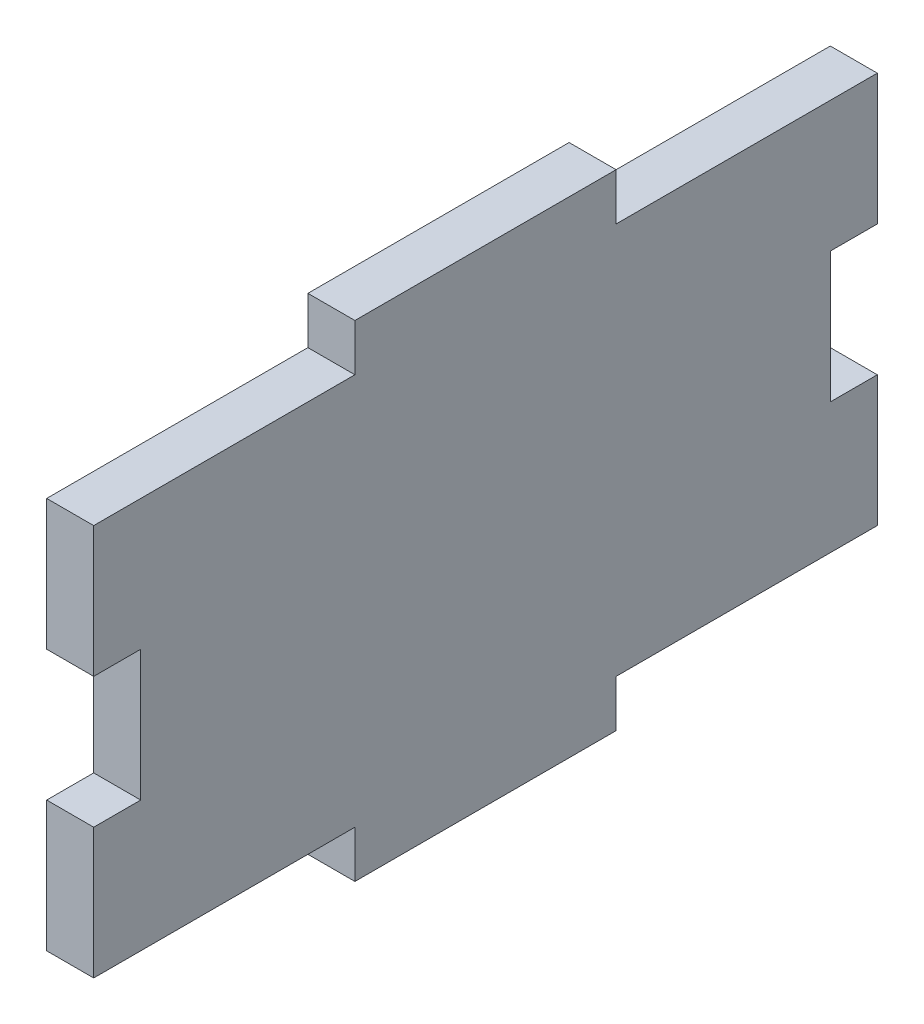
SolidWorks part; units mm, degrees
ref_plane "Front Plane" through (0, 0, 0) normal (0, 0, 1) x (1, 0, 0)
ref_plane "Top Plane" through (0, 0, 0) normal (0, 1, 0) x (1, 0, 0)
ref_plane "Right Plane" through (0, 0, 0) normal (1, 0, 0) x (0, 0, -1)
sketch "Sides" plane through (0, 0, 0) normal (1, 0, 0) x (0, 0, -1)
  line L0 (0, 16.6667) -> (0, 25)
  line L1 (0, 0) -> (16.6667, 0)
  line L2 (0, 0) -> (0, 8.3333)
  line L3 (0, 25) -> (16.6667, 25)
  line L4 (50, 0) -> (50, 8.3333)
  line L5 (0, 16.6667) -> (3, 16.6667)
  line L6 (33.3333, 25) -> (50, 25)
  line L7 (0, 8.3333) -> (3, 8.3333)
  line L8 (3, 16.6667) -> (3, 8.3333)
  line L9 (33.3333, 0) -> (50, 0)
  line L10 (16.6667, 25) -> (16.6667, 28)
  line L11 (16.6667, 28) -> (33.3333, 28)
  line L12 (33.3333, 25) -> (33.3333, 28)
  line L13 (50, 16.6667) -> (50, 25)
  line L14 (33.3333, 0) -> (33.3333, -3)
  line L15 (16.6667, 0) -> (16.6667, -3)
  line L16 (16.6667, -3) -> (33.3333, -3)
  line L17 (50, 16.6667) -> (47, 16.6667)
  line L18 (50, 8.3333) -> (47, 8.3333)
  line L19 (47, 16.6667) -> (47, 8.3333)
  dimension "D1" = 25
  dimension "D2" = 50
  dimension "D3" = 8.3333
  dimension "D4" = 8.3333
  dimension "D5" = 3
  dimension "D6" = 16.6667
  dimension "D7" = 3
  dimension "D8" = 16.6667
extrude "Sides Extruded" add sketch "Sides" along normal blind 3
sketch "Sketch1" plane through (0, 0, 0) normal (-1, 0, 0) x (0, 0, 1)
  line L1 (-40.3315, 22.2137) -> (-28.5315, 22.2137)
  line L2 (-40.3315, 22.2137) -> (-40.3315, 11.7637)
  line L3 (-40.3315, 11.7637) -> (-28.5315, 11.7637)
  line L4 (-28.5315, 22.2137) -> (-28.5315, 11.7637)
  line L5 (-8.5315, 21.4637) -> (0.4685, 21.4637)
  line L6 (-8.5315, 21.4637) -> (-8.5315, 10.7637)
  line L7 (-8.5315, 10.7637) -> (0.4685, 10.7637)
  line L8 (0.4685, 21.4637) -> (0.4685, 10.7637)
  dimension "D1" = 10.45
  dimension "D2" = 11.8
  dimension "D3" = 9
  dimension "D4" = 10.7
  dimension "D5" = 20
  dimension "D6" = 1
